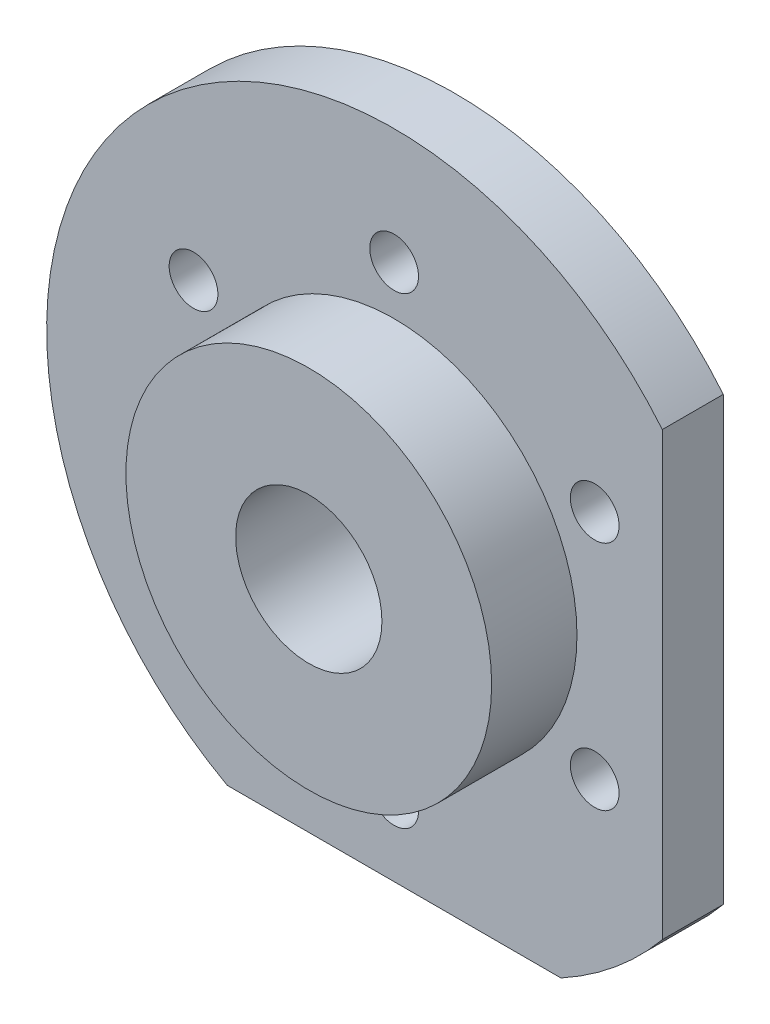
SolidWorks part; units mm, degrees
material "Alumina"
ref_plane "Front Plane" through (0, 0, 0) normal (0, 0, 1) x (1, 0, 0)
ref_plane "Top Plane" through (0, 0, 0) normal (0, 1, 0) x (1, 0, 0)
ref_plane "Right Plane" through (0, 0, 0) normal (1, 0, 0) x (0, 0, -1)
sketch "Sketch1" plane through (0, 0, 0) normal (0, 0, 1) x (1, 0, 0)
  line L0 (0, 0) -> (50000, 0) construction
  line L1 (0, 0) -> (0, 50000) construction
  line L2 (22, 18.1177) -> (22, -18.1177)
  line L3 (13.6839, -25) -> (-13.6839, -25)
  arc A0 (22, 18.1177) -> (-13.6839, -25) centre (0, 0) ccw
  circle A1 centre (0, 0) radius 15
  circle A2 centre (0, 0) radius 19 construction
  arc A3 (13.6839, -25) -> (22, -18.1177) centre (0, 0) ccw
  circle A4 centre (0, 19) radius 2
  circle A5 centre (16.4545, 9.5) radius 2
  circle A6 centre (16.4545, -9.5) radius 2
  circle A7 centre (0, -19) radius 2
  circle A8 centre (-16.4545, -9.5) radius 2
  circle A9 centre (-16.4545, 9.5) radius 2
  circle A10 centre (0, 0) radius 6
  circle A11 centre (0, 0) radius 4
  point P28 (0, 0)
  dimension "D1" = 57
  dimension "D2" = 38
  dimension "D3" = 30
  dimension "D6" = 4
  dimension "D8" = 12
  dimension "D4" = 22
  dimension "D5" = 25
  dimension "D7" = 6
extrude "Boss-Extrude1" add sketch "Sketch1" against normal blind 1 contours A1 A10 | A10 A11 region at (-14.5757, 0, 0) region at (-5.8303, 0, 0)
extrude "Boss-Extrude2" add sketch "Sketch1<4>" along normal blind 5 separate body contours L3 A3 L2 A0 A9 A8 A7 A6 A5 A4 A1 region at (21.2643, 0, 0)
sketch "Sketch1<4>" plane through (0, 0, 0) normal (0, 0, 1) x (1, 0, 0) same geometry as "Sketch1"
extrude "Boss-Extrude3" add sketch "Sketch1<6>" along normal blind 12 contours A1 A10 region at (-14.5757, 0, 0)
sketch "Sketch1<6>" plane through (0, 0, 0) normal (0, 0, 1) x (1, 0, 0) same geometry as "Sketch1"
cosmetic thread "Cosmetic Thread1" parameters "D2"=14
extrude "Boss-Extrude4" add sketch "Sketch1<7>" along normal blind 2 contours A10 A11 region at (-5.8303, 0, 0)
sketch "Sketch1<7>" plane through (0, 0, 0) normal (0, 0, 1) x (1, 0, 0) same geometry as "Sketch1"
